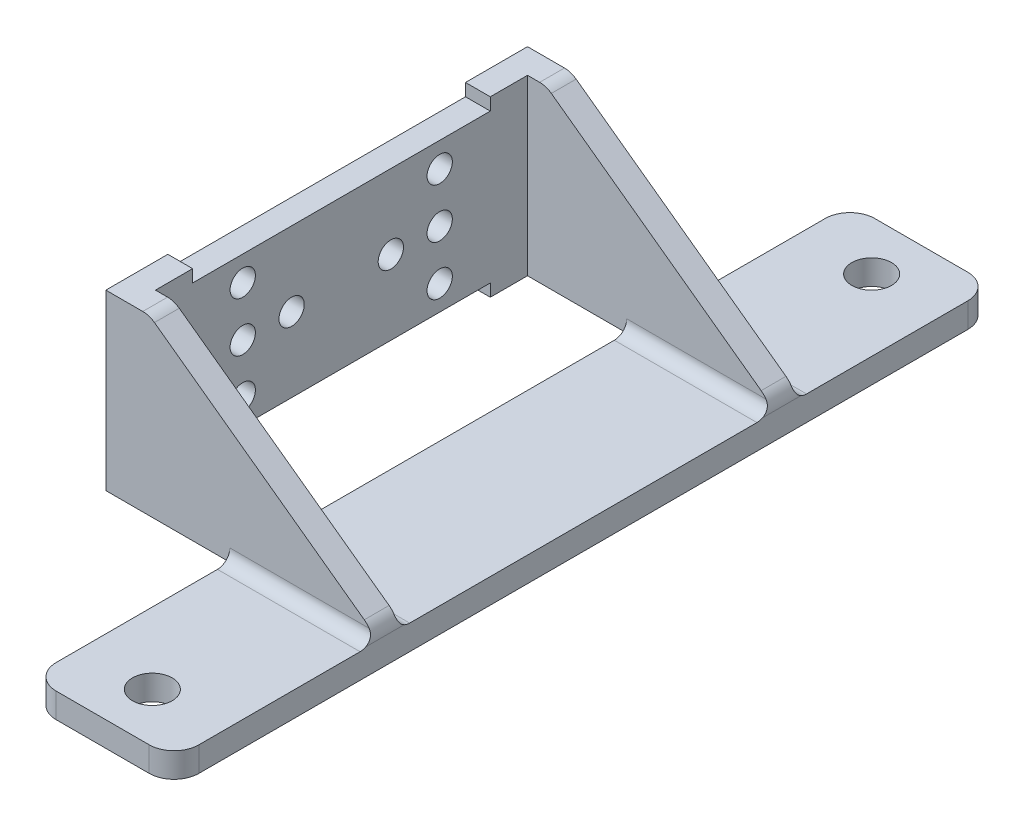
SolidWorks part; units mm, degrees
ref_plane "Front Plane" through (0, 0, 0) normal (0, 0, 1) x (1, 0, 0)
ref_plane "Top Plane" through (0, 0, 0) normal (0, 1, 0) x (1, 0, 0)
ref_plane "Right Plane" through (0, 0, 0) normal (1, 0, 0) x (0, 0, -1)
sketch "Sketch1" plane through (0, -83.5299, 0) normal (0, 1, 0) x (1, 0, 0)
  line L0 (103.5839, -152.0187) -> (122.3339, -152.0187)
  line L1 (127.3339, -147.0187) -> (127.3339, 7.9813)
  line L2 (103.5839, 12.9813) -> (122.3339, 12.9813)
  line L3 (98.5839, 7.9813) -> (98.5839, -147.0187)
  arc A0 (98.5839, 7.9813) -> (103.5839, 12.9813) centre (103.5839, 7.9813) cw
  arc A1 (122.3339, 12.9813) -> (127.3339, 7.9813) centre (122.3339, 7.9813) cw
  arc A2 (98.5839, -147.0187) -> (103.5839, -152.0187) centre (103.5839, -147.0187) ccw
  arc A3 (127.3339, -147.0187) -> (122.3339, -152.0187) centre (122.3339, -147.0187) cw
  arc A4 (122.3339, -152.0187) -> (127.3339, -147.0187) centre (122.3339, -147.0187) ccw construction
  circle A5 centre (112.9589, -142.0187) radius 4
  circle A6 centre (112.9589, 2.9813) radius 4
extrude "Boss-Extrude1" add sketch "Sketch1" along normal blind 5
sketch "Sketch2" plane through (127.3339, 0, 0) normal (1, 0, 0) x (0, 0, -1)
  line L0 (-147.0187, -78.5299) -> (7.9813, -78.5299) construction
  line L1 (-107.0187, -78.5299) -> (-112.0187, -78.5299)
  line L2 (-107.0187, -78.5299) -> (-107.0187, -43.5299)
  line L3 (-107.0187, -43.5299) -> (-112.0187, -43.5299)
  line L4 (-112.0187, -78.5299) -> (-112.0187, -43.5299)
  line L5 (-152.0187, -78.5299) -> (-152.0187, -83.5299) construction
  line L6 (-27.0187, -78.5299) -> (-32.0187, -78.5299)
  line L7 (-27.0187, -78.5299) -> (-27.0187, -43.5299)
  line L8 (-27.0187, -43.5299) -> (-32.0187, -43.5299)
  line L9 (-32.0187, -78.5299) -> (-32.0187, -43.5299)
  line L10 (12.9813, -78.5299) -> (12.9813, -83.5299) construction
  dimension "D1" = 40
  dimension "D2" = 5
  dimension "D3" = 5
  dimension "D4" = 35
  dimension "D5" = 40
extrude "Boss-Extrude2" add sketch "Sketch2" against normal up to surface (53.75 mm away)
sketch "Sketch3" plane through (73.5839, 0, 0) normal (-1, 0, 0) x (0, 0, 1)
  line L1 (32.0187, -43.5299) -> (107.0187, -43.5299)
  line L2 (32.0187, -43.5299) -> (32.0187, -78.5299)
  line L3 (32.0187, -78.5299) -> (107.0187, -78.5299)
  line L4 (107.0187, -43.5299) -> (107.0187, -78.5299)
  circle A0 centre (49.7187, -61.0299) radius 2.55
  circle A1 centre (89.4187, -61.0299) radius 2.55
  circle A2 centre (89.4187, -71.0299) radius 2.55
  circle A3 centre (89.4187, -51.0299) radius 2.55
  circle A4 centre (49.7187, -51.0299) radius 2.55
  circle A5 centre (49.7187, -71.0299) radius 2.55
  circle A6 centre (59.5687, -61.0299) radius 2.55
  circle A7 centre (79.5687, -61.0299) radius 2.55
extrude "Boss-Extrude3" add sketch "Sketch3" against normal blind 5
chamfer "Chamfer1" distance 45 angle 36 2 edges at (127.3339, -43.5299, 109.5187) (127.3339, -43.5299, 29.5187) first distance on face at (101.7089, -43.5299, 69.5187)
fillet "Fillet1" radius 4 4 edges at (82.3339, -43.5299, 109.5187) (127.3339, -76.2243, 109.5187) (127.3339, -76.2243, 29.5187) (82.3339, -43.5299, 29.5187)
fillet "Fillet2" radius 2.5 4 edges at (112.9589, -78.5299, 27.0187) (112.9589, -78.5299, 107.0187) (112.9589, -78.5299, 112.0187) (112.9589, -78.5299, 32.0187)
sketch "Sketch4" plane through (78.5839, 0, 0) normal (1, 0, 0) x (0, 0, -1)
  line L0 (-107.0187, -43.5299) -> (-32.0187, -43.5299) construction
  line L1 (-99.5187, -41.0299) -> (-39.5187, -41.0299)
  line L2 (-99.5187, -41.0299) -> (-99.5187, -46.0299)
  line L3 (-99.5187, -46.0299) -> (-39.5187, -46.0299)
  line L4 (-39.5187, -41.0299) -> (-39.5187, -46.0299)
  line L5 (-99.5187, -41.0299) -> (-39.5187, -46.0299) construction
  line L6 (-99.5187, -46.0299) -> (-39.5187, -41.0299) construction
  line L7 (-104.5187, -78.5299) -> (-34.5187, -78.5299) construction
  line L8 (-99.5187, -76.0299) -> (-39.5187, -76.0299)
  line L9 (-99.5187, -76.0299) -> (-99.5187, -81.0299)
  line L10 (-99.5187, -81.0299) -> (-39.5187, -81.0299)
  line L11 (-39.5187, -76.0299) -> (-39.5187, -81.0299)
  line L12 (-99.5187, -76.0299) -> (-39.5187, -81.0299) construction
  line L13 (-99.5187, -81.0299) -> (-39.5187, -76.0299) construction
  point P0 (-69.5187, -43.5299)
  point P7 (-69.5187, -78.5299)
extrude "Cut-Extrude1" cut sketch "Sketch4" against normal up to surface (5 mm away) up to face at (73.5839, -61.0299, 69.5187)
